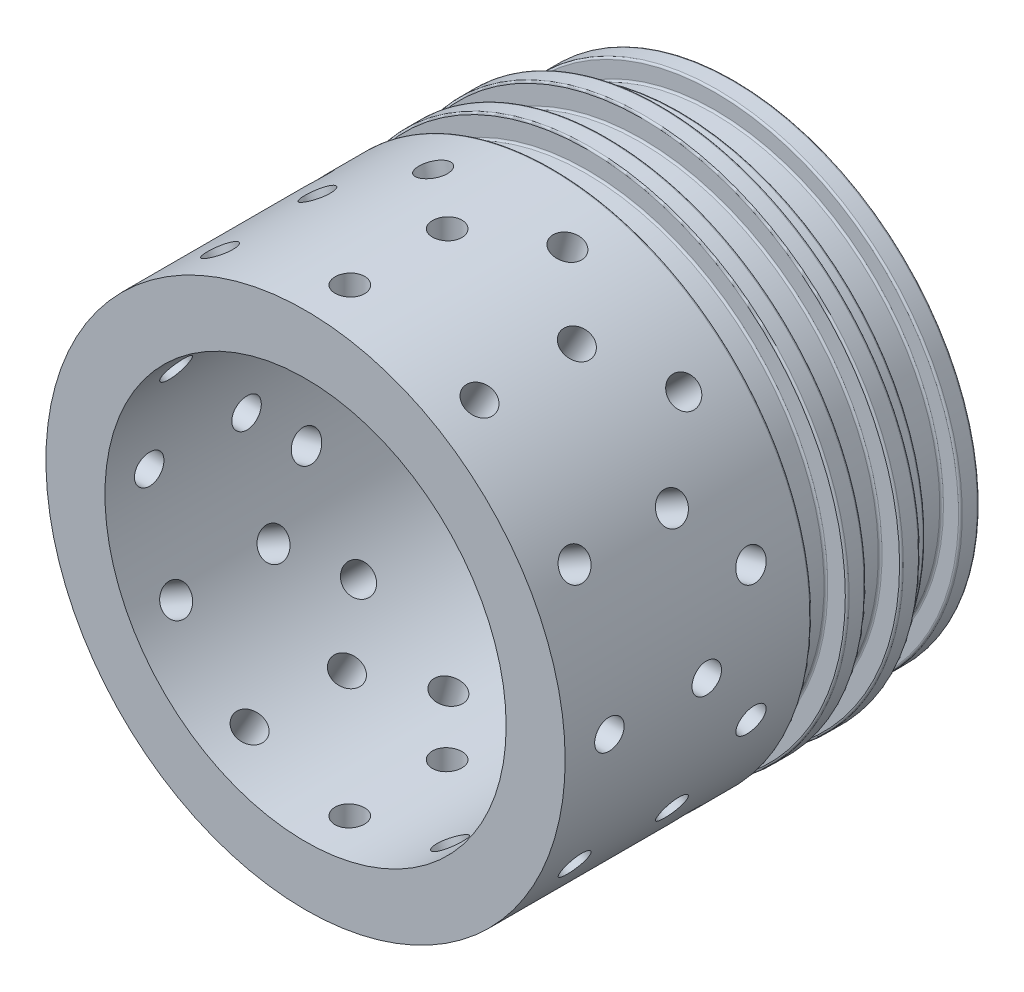
SolidWorks part; units mm, degrees
other "Markup1"
sketch "Sketch12" plane through (69.85, -69.85, 115.2525) normal (0.9938, -0.0067, 0.111) x (0.1108, -0.0236, -0.9936)
ref_plane "Front Plane" through (0, 0, 0) normal (0, 0, 1) x (1, 0, 0)
ref_plane "Top Plane" through (0, 0, 0) normal (0, 1, 0) x (1, 0, 0)
ref_plane "Right Plane" through (0, 0, 0) normal (1, 0, 0) x (0, 0, -1)
sketch "Sketch3" plane through (0, 0, 0) normal (1, 0, 0) x (0, 0, -1)
  line L0 (0, 0) -> (0, 66.0146)
  line L1 (0, 66.0146) -> (-5.08, 66.0146)
  line L2 (-19.685, 66.0146) -> (-19.685, 69.85)
  line L3 (-19.685, 69.85) -> (-24.765, 69.85)
  line L4 (-91.44, 69.85) -> (-91.44, 53.975)
  line L5 (-91.44, 53.975) -> (-6.35, 53.975)
  line L6 (-6.35, 53.975) -> (-6.35, 0)
  line L7 (-6.35, 0) -> (0, 0)
  line L8 (-48.895, 69.85) -> (-91.44, 69.85)
  line L10 (-48.895, 69.85) -> (-48.895, 64.1096)
  line L11 (-48.895, 64.1096) -> (-39.37, 64.1096)
  line L12 (-39.37, 69.85) -> (-39.37, 64.1096)
  line L14 (-34.29, 69.85) -> (-34.29, 64.1096)
  line L15 (-34.29, 64.1096) -> (-24.765, 64.1096)
  line L16 (-24.765, 69.85) -> (-24.765, 64.1096)
  line L18 (-14.605, 66.0146) -> (-14.605, 60.96)
  line L19 (-14.605, 60.96) -> (-5.08, 60.96)
  line L20 (-5.08, 66.0146) -> (-5.08, 60.96)
  line L21 (-34.29, 69.85) -> (-39.37, 69.85)
  line L22 (-14.605, 66.0146) -> (-19.685, 66.0146)
  line L23 (-48.895, 63.1825) -> (-39.37, 63.1825) construction
  line L24 (-44.1325, 66.675) -> (-44.1325, 63.1825) construction
  line L25 (-14.605, 60.0075) -> (-5.08, 60.0075) construction
  line L26 (-9.8425, 63.5) -> (-9.8425, 60.0075) construction
  circle A0 centre (-44.1325, 66.675) radius 3.4925 construction
  circle A1 centre (-9.8425, 63.5) radius 3.4925 construction
  point P21 (-3.175, 0)
  point P28 (-44.1325, 64.1096)
  point P32 (-9.8425, 60.96)
  dimension "D15" = 6.985
  dimension "D16" = 60.0075
  dimension "D17" = 6.985
  dimension "D1" = 6.35
  dimension "D2" = 15.875
  dimension "D3" = 71.755
  dimension "D4" = 60.96
  dimension "D5" = 69.85
  dimension "D6" = 66.0146
  dimension "D7" = 9.525
  dimension "D8" = 64.1096
  dimension "D9" = 5.08
  dimension "D10" = 5.08
  dimension "D11" = 5.08
  dimension "D12" = 9.525
  dimension "D13" = 5.08
  dimension "D14" = 63.1825
revolve "Revolve1" add sketch "Sketch3" angle 360 about L7
sketch "Sketch5" plane through (0, 0, 0) normal (0, 0, -1) x (-1, 0, 0)
  circle A0 centre (0, 0) radius 12.7 construction
  circle A1 centre (0, 0) radius 19.05
  circle A2 centre (0, 0) radius 3.81
  dimension "D1" = 25.4
  dimension "D2" = 7.62
  dimension "0.25" = 6.35
extrude "Boss-Extrude1" add sketch "Sketch5" against normal blind 50.8
extrude "Cut-Extrude1" cut sketch "Sketch5<2>" against normal blind 50.8 contours A2
sketch "Sketch5<2>" plane through (0, 0, 0) normal (0, 0, -1) x (-1, 0, 0) same geometry as "Sketch5"
fillet "Fillet1" radius 5.08 2 edges at (0, -53.975, 6.35) (0, 19.05, 6.35)
sketch "Sketch7" plane through (0, 0, 0) normal (1, 0, 0) x (0, 0, -1)
  line L0 (-91.44, 69.85) -> (-91.44, -69.85) construction
  line L1 (-91.44, 69.85) -> (-91.44, -69.85) construction
  line L2 (0, 0) -> (-91.44, 0) construction
  circle A0 centre (-77.1525, 0) radius 3.9688
  dimension "D2" = 7.9375
  dimension "D1" = 14.2875
extrude "Cut-Extrude2" cut sketch "Sketch7" along normal through all
ref_axis "Axis1" through (0, 0, 82.1441) along (0, 0, -1)
ref_plane "Plane1" through (0, 0, 0) normal (0.9659, -0.2588, 0) x (0, 0, -1)
sketch "Sketch8" plane through (0, 0, 0) normal (0.9659, -0.2588, 0) x (0, 0, -1)
  line L0 (-91.44, 69.85) -> (-91.44, -69.85) construction
  line L1 (-91.44, 69.85) -> (-91.44, -69.85) construction
  line L2 (-82.1441, 0) -> (-31.3441, 0) construction
  circle A0 centre (-62.865, 0) radius 3.9687
  dimension "D2" = 7.9375
  dimension "D1" = 28.575
extrude "Cut-Extrude3" cut sketch "Sketch8" along normal through all
pattern_circular "CirPattern1" count 12 over 360 about axis through (0, 0, 82.1441) along (0, 0, -1) of "Cut-Extrude2", "Cut-Extrude3"
fillet "Fillet2" radius 0.508 14 edges at (0, -66.0146, 5.08) (0, -60.96, 5.08) (0, -60.96, 14.605) (0, -66.0146, 14.605) (0, -69.85, 24.765) (0, -64.1096, 24.765) (0, -64.1096, 34.29) (0, -69.85, 34.29) (0, -69.85, 39.37) (0, -64.1096, 39.37) (0, -64.1096, 48.895) (0, -69.85, 48.895) (0, -66.0146, 0) (0, -69.85, 19.685)
sketch "Sketch9" plane through (0, 0, 91.44) normal (0, 0, 1) x (1, 0, 0)
  circle A0 centre (0, 0) radius 69.85
  circle A1 centre (0, 0) radius 53.975
extrude "Boss-Extrude2" add sketch "Sketch9" along normal blind 23.8125
sketch "Sketch10" plane through (0, 0, 0) normal (1, 0, 0) x (0, 0, -1)
  line L0 (-115.2525, 69.85) -> (-115.2525, -69.85) construction
  circle A0 centre (-103.3462, 0) radius 3.9687
  dimension "D1" = 7.9375
  dimension "D2" = 11.9062
extrude "Cut-Extrude4" cut sketch "Sketch10" along normal through all
pattern_circular "CirPattern2" count 12 over 360 about axis through (0, 0, 82.1441) along (0, 0, -1) of "Cut-Extrude4"
ref_plane "Plane2" through (0, 0, 91.44) normal (0, 0, 1) x (1, 0, 0)
